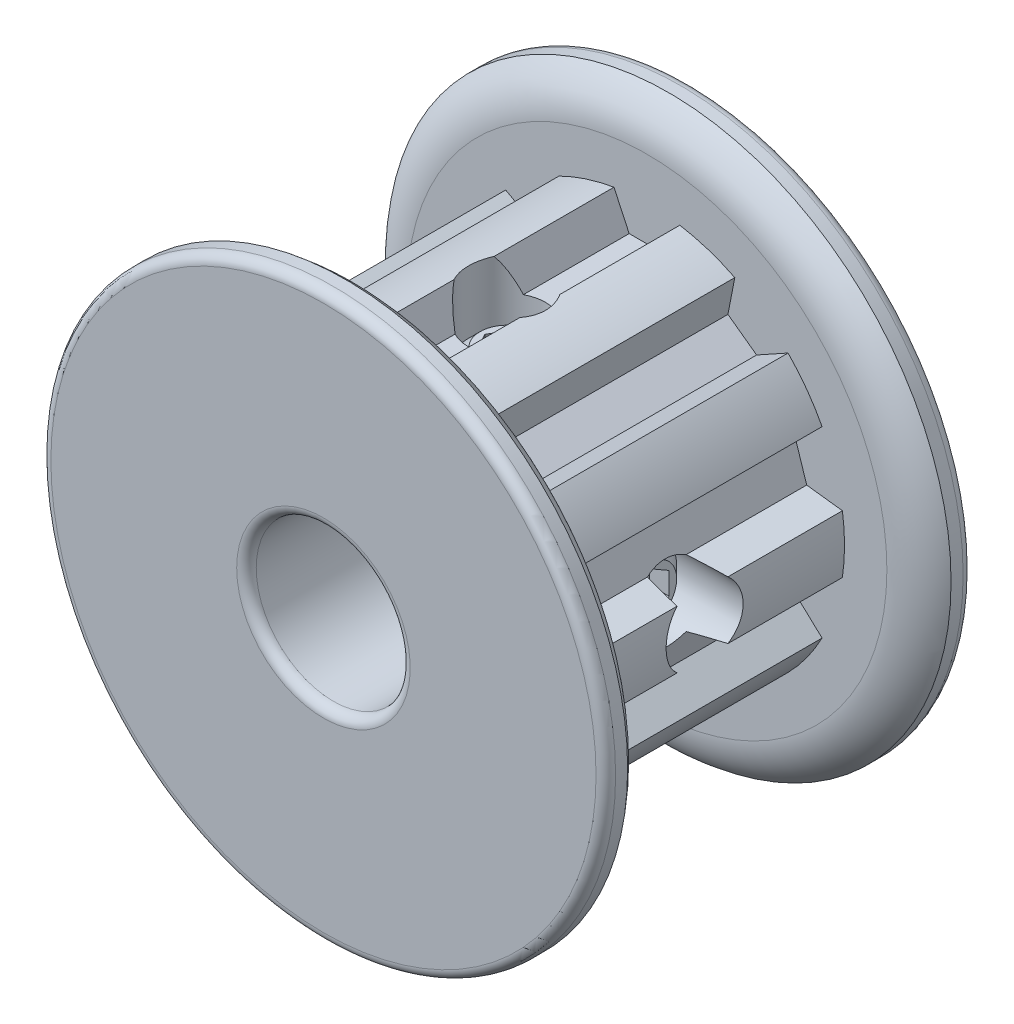
SolidWorks part; units mm, degrees
ref_plane "Front Plane" through (0, 0, 0) normal (0, 0, 1) x (1, 0, 0)
ref_plane "Top Plane" through (0, 0, 0) normal (0, 1, 0) x (1, 0, 0)
ref_plane "Right Plane" through (0, 0, 0) normal (1, 0, 0) x (0, 0, -1)
sketch "Sketch1" plane through (0, 0, 0) normal (0, 0, 1) x (1, 0, 0)
  line L0 (-1.2827, 7.592) -> (-0.6905, 6.322)
  line L1 (-0.6905, 6.322) -> (0.6905, 6.322)
  line L2 (0.6905, 6.322) -> (1.2827, 7.592)
  line L3 (-1.2827, 7.592) -> (1.2827, 7.592)
  line L4 (0, 0) -> (0, 6.322) construction
  line L5 (0, 6.322) -> (0, 8.608) construction
  circle A0 centre (0, 0) radius 8.1 construction
  circle A1 centre (0, 0) radius 11 construction
  circle A2 centre (0, 0) radius 7.6996 construction
  point P6 (0, 7.592)
  point P11 (0, 8.1)
  point P13 (0, 11)
  point P14 (0, 7.6996)
  dimension "D1" = 1.016
  dimension "PD" = 16.2
  dimension "D2" = 0.508
  dimension "OD" = 22
  dimension "b" = 50
  dimension "bt" = 2.5654
  dimension "ht" = 1.27
  dimension "hs" = 2.286
sketch "Sketch2" plane through (0, 0, 0) normal (1, 0, 0) x (0, 0, -1)
  line L0 (-7.15, 3) -> (7.15, 3)
  line L3 (-7.15, 3) -> (-7.15, 11)
  line L4 (-7.15, 11) -> (-5.45, 11) construction
  line L5 (-5.45, 11) -> (-5.45, 7.6996) construction
  line L6 (-5.45, 7.6996) -> (5.45, 7.6996)
  line L7 (5.45, 7.6996) -> (5.45, 11) construction
  line L8 (5.45, 11) -> (7.15, 11) construction
  line L9 (7.15, 11) -> (7.15, 3)
  line L10 (-7.15, 0) -> (7.15, 0) construction
  line L13 (-7.15, 11) -> (-6.3, 11)
  line L14 (-5.45, 9.3498) -> (-5.45, 7.6996)
  line L15 (5.45, 7.6996) -> (5.45, 9.3498)
  line L16 (6.3, 11) -> (7.15, 11)
  arc A0 (-5.45, 9.3498) -> (-6.3, 11) centre (-7.4769, 9.3498) ccw
  arc A1 (5.45, 9.3498) -> (6.3, 11) centre (7.4769, 9.3498) cw
  point P12 (-5.45, 9.3498)
  point P14 (-6.3, 11)
  point P20 (5.45, 9.3498)
  point P21 (6.3, 11)
  point P25 (5.45, 0)
  point P26 (-5.45, 0)
  dimension "OA" = 14.3
  dimension "Bore" = 6
  dimension "Outside Width" = 14.3
  dimension "Inside Width" = 10.9
revolve "Revolve1" add sketch "Sketch2" angle 360 mid plane about L10
sketch "Sketch3" plane through (0, 0, 0) normal (0, 0, 1) x (1, 0, 0)
  line L0 (-0.6905, 6.322) -> (0.6905, 6.322) construction
  line L1 (0.6905, 6.322) -> (1.2827, 7.592) construction
  line L2 (-1.2827, 7.592) -> (-0.6905, 6.322) construction
  line L3 (-0.6905, 6.322) -> (0.6905, 6.322)
  line L4 (0.6905, 6.322) -> (1.2827, 7.592)
  line L5 (-1.2827, 7.592) -> (-0.6905, 6.322)
  circle A0 centre (0, 0) radius 7.6996 construction
  arc A1 (1.2827, 7.592) -> (-1.2827, 7.592) centre (0, 0) ccw
extrude "Cut-Extrude1" cut sketch "Sketch3" against normal up to vertex (5.45 mm away) from vertex up to point (0, 7.6996, -5.45) starting at point (0, 7.6996, 5.45)
pattern_circular "CirPattern1" count 10 over 360 about axis through (0, 0, 7.15) along (0, 0, 1) of "Cut-Extrude1"
fillet "Fillet1" radius 0.381 4 edges at (3, 0, -7.15) (11, 0, -7.15) (11, 0, 7.15) (3, 0, 7.15)
sketch "Sketch5" plane through (0, 0, 0) normal (0, 1, 0) x (1, 0, 0)
  line L1 (1.2827, 0) -> (-1.2827, 0) construction
  line L2 (1.2827, 5.45) -> (1.2827, -5.45) construction
  line L3 (-1.2827, 5.45) -> (-1.2827, -5.45) construction
  circle A0 centre (0, 0) radius 1.5
extrude "Cut-Extrude2" cut sketch "Sketch5" along normal through all
sketch "Sketch6" plane through (0, 0, 0) normal (1, 0, 0) x (0, 0, -1)
  line L0 (0, 5.56) -> (0, 3.762)
  line L1 (6.769, 3) -> (-6.769, 3) construction
  line L3 (1.5, 6.322) -> (-1.5, 6.322) construction
  line L4 (-1.3316, 6.322) -> (-1.5, 6.322) construction
  line L5 (1.5, 6.322) -> (1.3316, 6.322) construction
  line L6 (0, 5.56) -> (-1.05, 5.56)
  line L7 (-1.05, 5.56) -> (-1.5, 5.11)
  line L8 (-1.5, 5.11) -> (-1.5, 4.212)
  line L9 (-1.5, 4.212) -> (-1.05, 3.762)
  line L10 (-1.05, 3.762) -> (0, 3.762)
  point P12 (0, 3)
  point P19 (0, 6.322)
  dimension "D1" = 0.762
  dimension "D2" = 0.762
  dimension "D3" = 135
  dimension "D4" = 0.45
revolve "Revolve2" add sketch "Sketch6" angle 360 about L0
sketch "Sketch7" plane through (0, 5.56, 0) normal (0, 1, 0) x (1, 0, 0)
  line L1 (0.866, 0) -> (0.433, 0.75)
  line L2 (0.433, 0.75) -> (-0.433, 0.75)
  line L3 (-0.433, 0.75) -> (-0.866, 0)
  line L4 (-0.866, 0) -> (-0.433, -0.75)
  line L5 (-0.433, -0.75) -> (0.433, -0.75)
  line L6 (0.433, -0.75) -> (0.866, 0)
  circle A0 centre (0, 0) radius 0.75 construction
  dimension "D1" = 1.5
extrude "Cut-Extrude3" cut sketch "Sketch7" against normal blind 0.75
pattern_circular "CirPattern2" count 2 over 270 of "Cut-Extrude2", "Revolve2", "Cut-Extrude3"
ref_axis "Center Axis 1" through (0, 0, -6.769) along (0, 0, 1)
ref_plane "Contact Plane 1" through (0, 0, 7.15) normal (0, 0, 1) x (1, 0, 0)
ref_plane "Contact Plane 2" through (0, 0, -7.15) normal (0, 0, -1) x (-1, 0, 0)
equation "\"D4@Sketch6\" = \"Set Screw Dia@Sketch5\" * .15"
equation "\"D1@Sketch7\" = \"Set Screw Dia@Sketch5\" / 2"
equation "\"D1@Cut-Extrude3\" = \"Set Screw Dia@Sketch5\" / 4"
